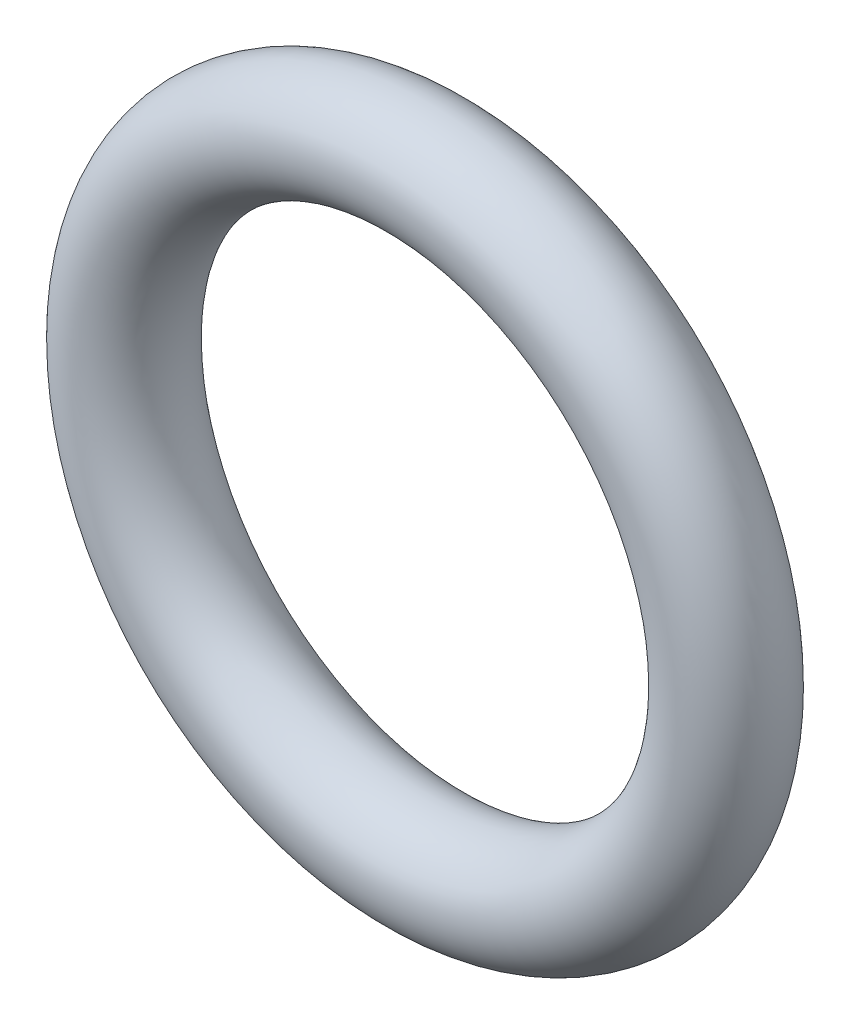
SolidWorks part; units mm, degrees
ref_plane "Front" through (0, 0, 0) normal (0, 0, 1) x (1, 0, 0)
ref_plane "Top" through (0, 0, 0) normal (0, 1, 0) x (1, 0, 0)
ref_plane "Right" through (0, 0, 0) normal (1, 0, 0) x (0, 0, -1)
sketch "Sketch1" plane through (0, 0, 0) normal (0, 0, 1) x (1, 0, 0)
  circle A0 centre (0, 0) radius 5.4
  dimension "d1" = 10.8
sketch "Sketch2" plane through (0, 0, 0) normal (0, 1, 0) x (1, 0, 0)
  circle A0 centre (-6.6, 0) radius 1.2
  point P2 (-5.4, 0)
  dimension "d2" = 2.4
sweep "Sweep1" add profiles "Sketch2" path "Sketch1"
ref_axis "Axis1" through (0, 0, -5.0798) along (0, 0, 1)
